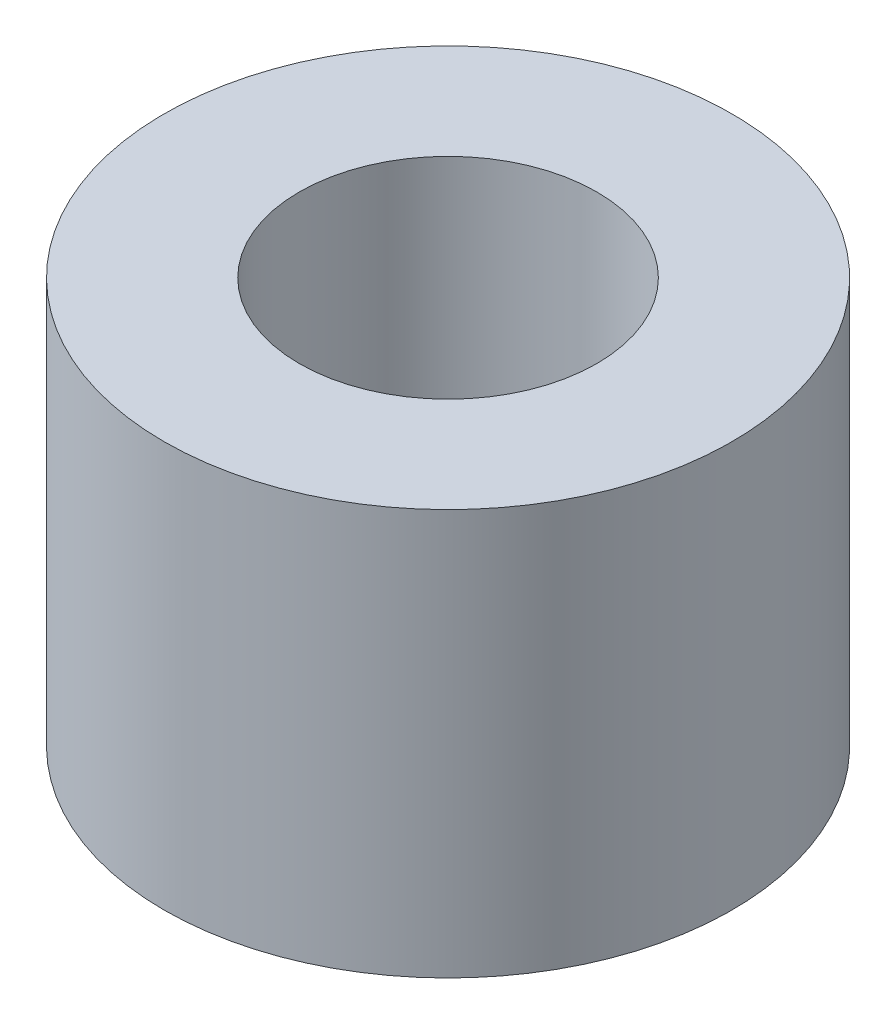
SolidWorks part; units mm, degrees
ref_plane "Front Plane" through (0, 0, 0) normal (0, 0, 1) x (1, 0, 0)
ref_plane "Top Plane" through (0, 0, 0) normal (0, 1, 0) x (1, 0, 0)
ref_plane "Right Plane" through (0, 0, 0) normal (1, 0, 0) x (0, 0, -1)
sketch "Sketch1" plane through (0, 0, 0) normal (0, 1, 0) x (1, 0, 0)
  circle A0 centre (0, 0) radius 5.5
  circle A1 centre (0, 0) radius 10.5
  dimension "D1" = 11
  dimension "D2" = 21
extrude "Boss-Extrude1" add sketch "Sketch1" along normal blind 15
